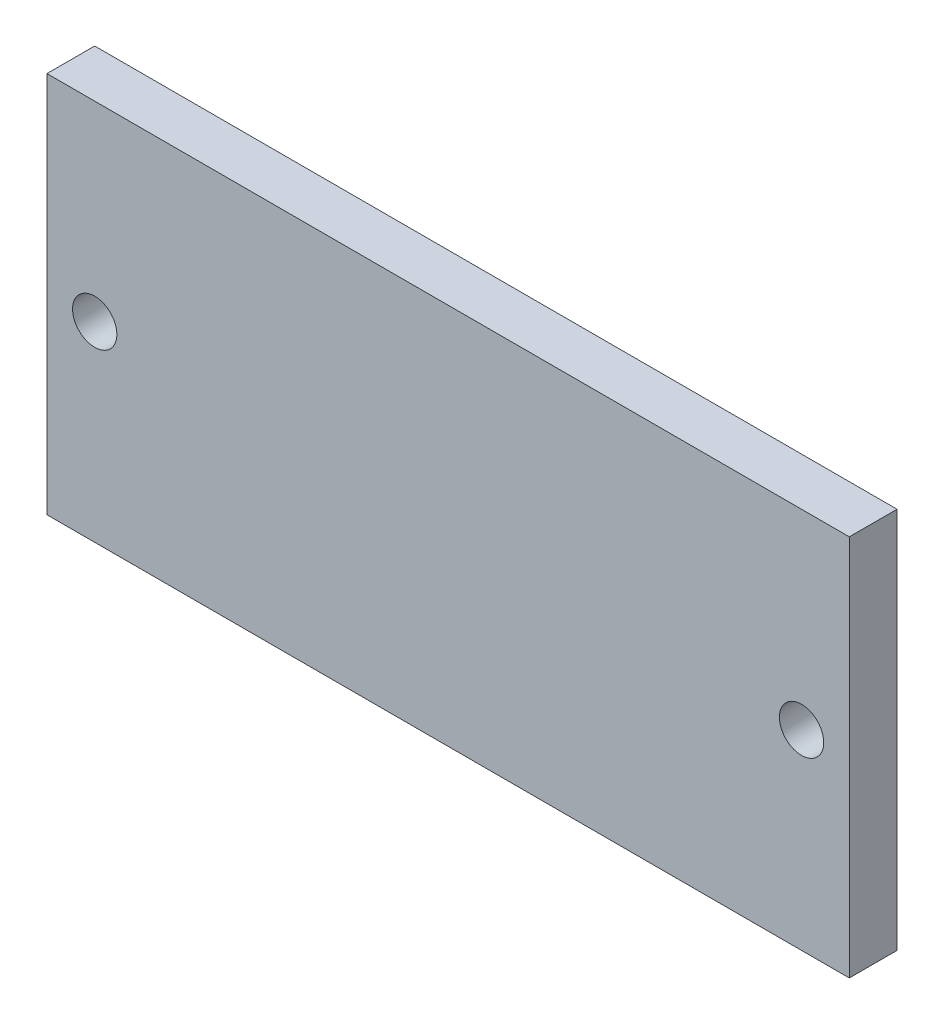
SolidWorks part; units mm, degrees
ref_plane "Front Plane" through (0, 0, 0) normal (0, 0, 1) x (1, 0, 0)
ref_plane "Top Plane" through (0, 0, 0) normal (0, 1, 0) x (1, 0, 0)
ref_plane "Right Plane" through (0, 0, 0) normal (1, 0, 0) x (0, 0, -1)
sketch "Sketch1" plane through (0, 0, 0) normal (0, 0, 1) x (1, 0, 0)
  line L0 (-26.67, 0) -> (26.67, 0) construction
  line L1 (26.67, -12.7) -> (-26.67, -12.7)
  line L2 (26.67, -12.7) -> (26.67, 12.7)
  line L3 (26.67, 12.7) -> (-26.67, 12.7)
  line L4 (-26.67, -12.7) -> (-26.67, 12.7)
  line L5 (0, 12.7) -> (0, -12.7) construction
  circle A0 centre (-23.495, 0) radius 1.4732
  circle A1 centre (23.495, 0) radius 1.4732
  dimension "D3" = 2.9464
  dimension "D1" = 53.34
  dimension "D2" = 25.4
  dimension "D4" = 3.175
extrude "Boss-Extrude1" add sketch "Sketch1" along normal blind 3.175
